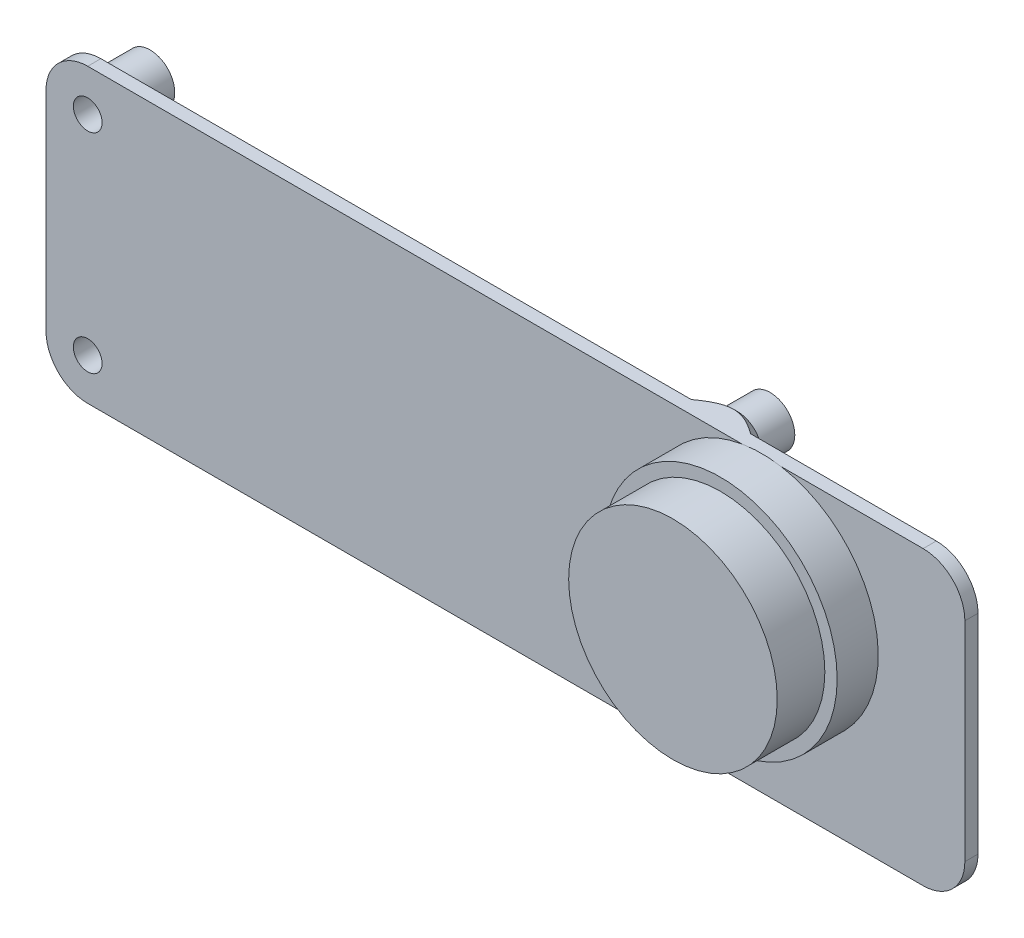
SolidWorks part; units mm, degrees
ref_plane "Front Plane" through (0, 0, 0) normal (0, 0, 1) x (1, 0, 0)
ref_plane "Top Plane" through (0, 0, 0) normal (0, 1, 0) x (1, 0, 0)
ref_plane "Right Plane" through (0, 0, 0) normal (1, 0, 0) x (0, 0, -1)
sketch "Sketch1" plane through (0, 0, 0) normal (0, 0, 1) x (1, 0, 0)
  line L1 (0, 5.08) -> (101.74, 5.08)
  line L2 (-5.08, 0) -> (-5.08, -25.4)
  line L3 (0, -30.48) -> (101.74, -30.48)
  line L4 (106.82, 0) -> (106.82, -25.4)
  circle A0 centre (0, 0) radius 1.75
  circle A1 centre (0, -25.4) radius 1.75
  circle A2 centre (75.51, 1.63) radius 1.75
  circle A3 centre (64.33, -27.48) radius 1.75
  arc A4 (-5.08, -25.4) -> (0, -30.48) centre (0, -25.4) ccw
  arc A5 (101.74, -30.48) -> (106.82, -25.4) centre (101.74, -25.4) ccw
  arc A6 (101.74, 5.08) -> (106.82, 0) centre (101.74, 0) cw
  arc A7 (0, 5.08) -> (-5.08, 0) centre (0, 0) ccw
  point P0 (0, 0)
  point P1 (75.51, 1.63)
  point P3 (64.33, -27.48)
  point P4 (0, -25.4)
  point P19 (-5.08, -30.48)
  point P22 (106.82, -30.48)
  dimension "D6" = 3.5
  dimension "D11" = 5.08
  dimension "D1" = 75.51
  dimension "D2" = 64.33
  dimension "D3" = 1.63
  dimension "D4" = 25.4
  dimension "D5" = 27.48
  dimension "D7" = 35.56
  dimension "D8" = 5.08
  dimension "D9" = 5.08
  dimension "D10" = 111.9
extrude "Boss-Extrude1" add sketch "Sketch1" along normal blind 1.6
sketch "Sketch2" plane through (0, 0, 1.6) normal (0, 0, 1) x (1, 0, 0)
  line L1 (106.82, -25.4) -> (106.82, 0) construction
  line L2 (101.74, 5.08) -> (0, 5.08) construction
  circle A0 centre (82.07, -8.92) radius 12.7
  dimension "D1" = 25.4
  dimension "D3" = 14
  dimension "D2" = 24.75
extrude "Boss-Extrude2" add sketch "Sketch2" along normal blind 10.8
sketch "Sketch3" plane through (0, 0, 0) normal (0, 0, -1) x (-1, 0, 0)
  circle A0 centre (0, 0) radius 1.75 construction
  circle A1 centre (0, -25.4) radius 1.75 construction
  circle A2 centre (-64.33, -27.48) radius 1.75 construction
  circle A3 centre (-75.51, 1.63) radius 1.75 construction
  circle A12 centre (0, 0) radius 1.75
  circle A13 centre (0, -25.4) radius 1.75
  circle A14 centre (-64.33, -27.48) radius 1.75
  circle A15 centre (-75.51, 1.63) radius 1.75
  circle A16 centre (-75.51, 1.63) radius 3
  circle A17 centre (-64.33, -27.48) radius 3
  circle A18 centre (0, -25.4) radius 3
  circle A19 centre (0, 0) radius 3
  dimension "D1" = 6
extrude "Boss-Extrude3" add sketch "Sketch3" along normal blind 6
sketch "Sketch4" plane through (0, 0, 1.6) normal (0, 0, 1) x (1, 0, 0)
  circle A0 centre (82.07, -8.92) radius 12.7 construction
  circle A1 centre (82.07, -8.92) radius 12.7
  circle A2 centre (82.07, -8.92) radius 14.2
  dimension "D1" = 1.5
extrude "Boss-Extrude4" add sketch "Sketch4" along normal blind 5
chamfer "Chamfer1" distance 2 angle 45 4 edges at (61.33, -27.48, 0) (3, -25.4, 0) (3, 0, 0) (78.51, 1.63, 0)
